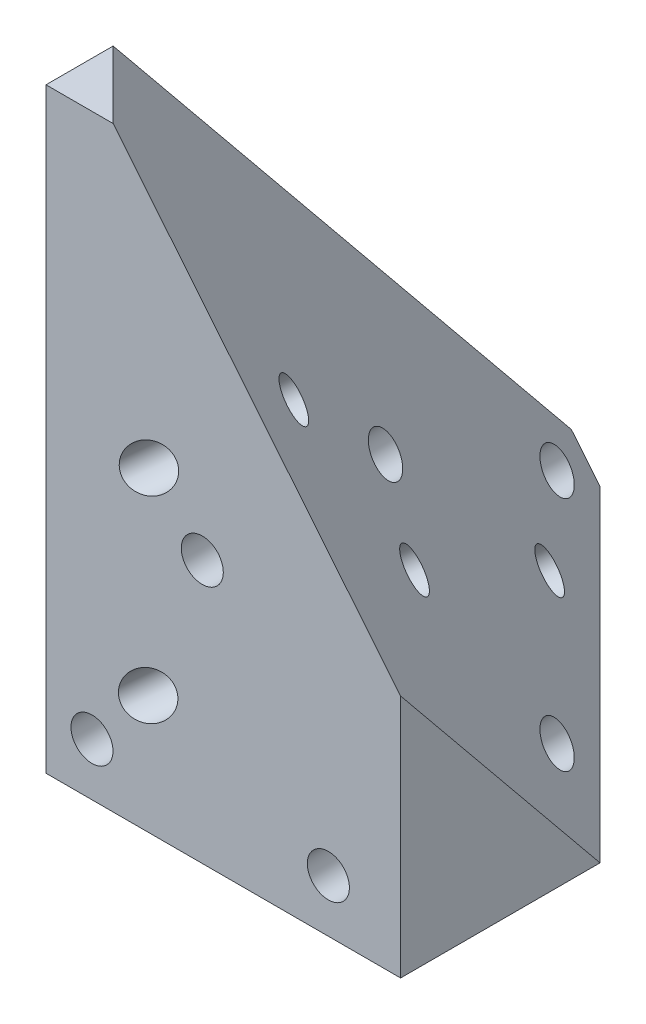
SolidWorks part; units mm, degrees
ref_plane "Front Plane" through (0, 0, 0) normal (0, 0, 1) x (1, 0, 0)
ref_plane "Top Plane" through (0, 0, 0) normal (0, 1, 0) x (1, 0, 0)
ref_plane "Right Plane" through (0, 0, 0) normal (1, 0, 0) x (0, 0, -1)
sketch "Sketch1" plane through (0, 0, 0) normal (0, 1, 0) x (1, 0, 0)
  line L0 (0, 0) -> (0, 20)
  line L2 (13.5, 0) -> (0, 0)
  line L3 (0, 20) -> (13.5, 20)
  line L4 (13.5, 20) -> (13.5, 0)
  dimension "D1" = 13.5
  dimension "D2" = 20
extrude "Boss-Extrude1" add sketch "Sketch1" along normal blind 22.7
ref_plane "Plane1" through (7.9092, 6.4578, -7.9092) normal (-0.6124, -0.5, 0.6124) x (0.7906, -0.3873, 0.4743)
sketch "Sketch2" plane through (7.9092, 6.4578, -7.9092) normal (-0.6124, -0.5, 0.6124) x (0.7906, -0.3873, 0.4743)
  line L1 (25.0062, -28.8765) -> (-25.0062, -28.8765)
  line L2 (25.0062, -28.8765) -> (25.0062, 28.8765)
  line L3 (25.0062, 28.8765) -> (-25.0062, 28.8765)
  line L4 (-25.0062, -28.8765) -> (-25.0062, 28.8765)
  line L5 (25.0062, -28.8765) -> (-25.0062, 28.8765) construction
  line L6 (25.0062, 28.8765) -> (-25.0062, -28.8765) construction
  point P0 (0, 0)
extrude "Cut-Extrude1" cut sketch "Sketch2" against normal through all
ref_plane "Plane2" through (-5.3897, 0, -5.3897) normal (-0.7071, 0, -0.7071) x (-0.7071, 0, 0.7071)
sketch "Sketch4" plane through (7.9092, 6.4578, -7.9092) normal (0.6124, 0.5, -0.6124) x (-0.4743, -0.3873, -0.7906)
  circle A0 centre (7.5975, -1.5053) radius 0.8 construction
  circle A1 centre (7.5975, -1.5053) radius 0.8 construction
  circle A2 centre (-6.516, 6.8355) radius 0.8 construction
  circle A3 centre (-3.5904, 1.0311) radius 0.8 construction
  circle A4 centre (-6.516, 6.8355) radius 0.8 construction
  circle A5 centre (-3.5904, 1.0311) radius 0.8 construction
hole_wizard "M2x0.4 Tapped Hole1" positions "3DSketch1" profile "Sketch5" tap size "M2x0.4" standard "ANSI Metric" end condition through all
sketch3d "3DSketch1"
  point P0 (6.6768, 14.2762, -2.7578)
  point P3 (8.9601, 8.6471, -5.0707)
  point P6 (5.2574, 2.3494, -13.9155)
sketch "Sketch5" plane through (6.6768, 14.2762, -2.7578) normal (0.4344, 0.4344, 0.7891) x (-0.6605, 0.7492, -0.0488)
  line L0 (0, 0) -> (0, 12.9156)
  line L1 (0, 12.9156) -> (0.8, 12.9156)
  line L2 (0.8, 12.9156) -> (0.8, 0)
  line L5 (0.8, 0) -> (0, 0)
  line L11 (0, -6.35) -> (0, 107.95) construction
  dimension "Thru Tap Drill Dia." = 1.6
  dimension "Thru Tap Drill Depth" = 12.9156
cosmetic thread "Hole Thread1" parameters "D2"=2
cosmetic thread "Hole Thread2" parameters "D2"=2
cosmetic thread "Hole Thread3" parameters "D2"=2
sketch "Sketch7" plane through (0, 0, 0) normal (0, 0, 1) x (1, 0, 0)
  circle A0 centre (10.75, 2) radius 1.2 construction
  circle A1 centre (10.75, 2) radius 1.2 construction
  circle A2 centre (1.75, 2) radius 1.2 construction
  circle A3 centre (1.75, 2) radius 1.2 construction
  circle A4 centre (5.95, 10) radius 1.2 construction
  circle A5 centre (5.95, 10) radius 1.2
hole_wizard "M2x0.4 Tapped Hole3" positions "3DSketch3" profile "Sketch9" tap size "M2x0.4" standard "ANSI Metric" end condition through all
sketch3d "3DSketch3"
  point P0 (5.95, 10, 0)
  point P3 (1.75, 2, 0)
  point P6 (10.75, 2, 0)
sketch "Sketch9" plane through (5.95, 10, 0) normal (1, 0, 0) x (0, -1, 0)
  line L0 (0, 0) -> (0, 20)
  line L1 (0, 20) -> (0.8, 20)
  line L2 (0.8, 20) -> (0.8, 0)
  line L5 (0.8, 0) -> (0, 0)
  line L11 (0, -6.35) -> (0, 107.95) construction
  dimension "Thru Tap Drill Dia." = 1.6
  dimension "Thru Tap Drill Depth" = 20
cosmetic thread "Hole Thread7" parameters "D1"=2.4, "D2"=2
cosmetic thread "Hole Thread8" parameters "D1"=2.4, "D2"=2
cosmetic thread "Hole Thread9" parameters "D1"=2.4, "D2"=2
